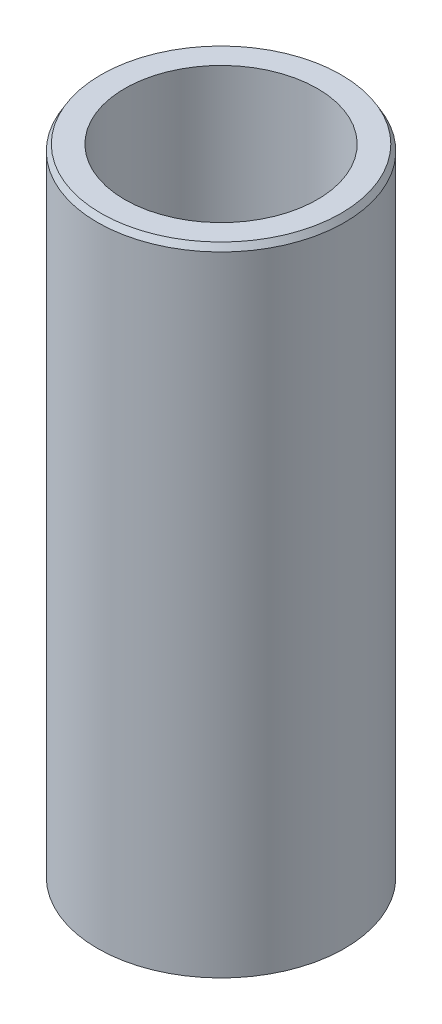
SolidWorks part; units mm, degrees
ref_plane "Front Plane" through (0, 0, 0) normal (0, 0, 1) x (1, 0, 0)
ref_plane "Top Plane" through (0, 0, 0) normal (0, 1, 0) x (1, 0, 0)
ref_plane "Right Plane" through (0, 0, 0) normal (1, 0, 0) x (0, 0, -1)
sketch "Sketch1" plane through (0, 0, 0) normal (0, 1, 0) x (1, 0, 0)
  circle A0 centre (0, 0) radius 52.5
  dimension "SHAFT_OD" = 105
extrude "Boss-Extrude1" add sketch "Sketch1" along normal blind 271.1757
sketch "Sketch2" plane through (0, 0, 0) normal (0, 1, 0) x (1, 0, 0)
  circle A0 centre (0, 0) radius 40.8971
  dimension "BORE_D" = 81.7941
extrude "Cut-Extrude1" cut sketch "Sketch2" along normal through all
chamfer "Chamfer1" distance 2.6038 angle 30 2 edges at (0, 271.1757, 52.5) (0, 0, 52.5) first distance on face at (0, 271.1757, 52.5) first distance on face at (0, 0, 40.8971)
